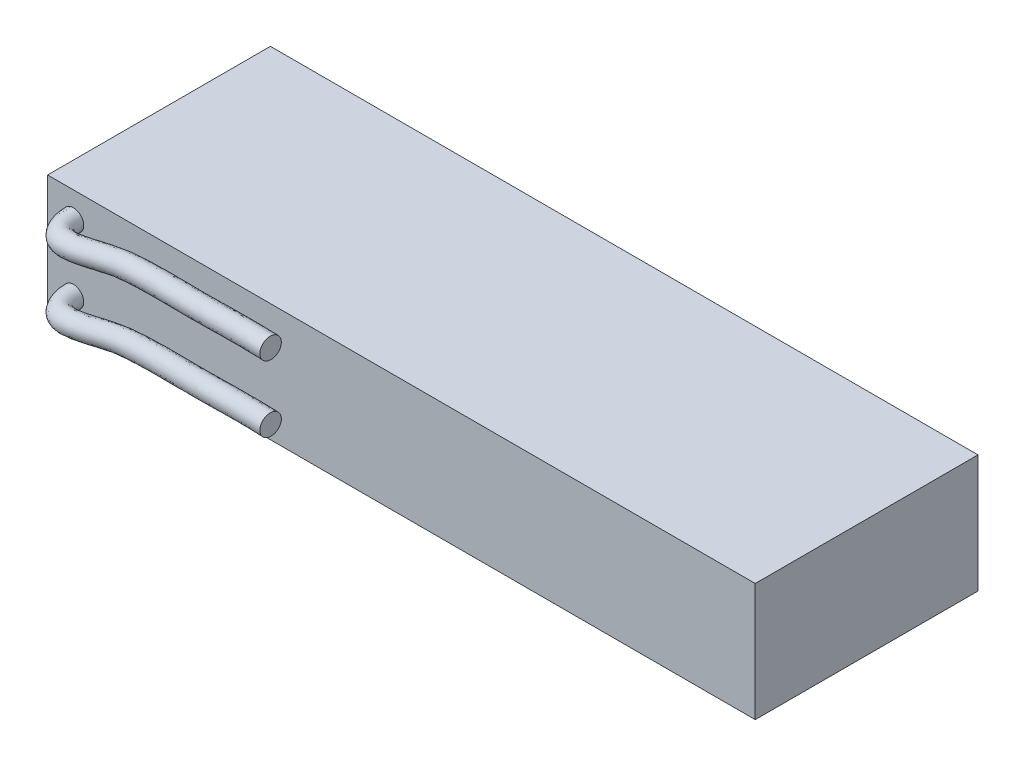
SolidWorks part; units mm, degrees
ref_plane "Front Plane" through (0, 0, 0) normal (0, 0, 1) x (1, 0, 0)
ref_plane "Top Plane" through (0, 0, 0) normal (0, 1, 0) x (1, 0, 0)
ref_plane "Right Plane" through (0, 0, 0) normal (1, 0, 0) x (0, 0, -1)
sketch "Sketch1" plane through (0, 0, 0) normal (0, 1, 0) x (1, 0, 0)
  line L1 (0, 0) -> (137.16, 0)
  line L2 (0, 0) -> (0, 43.18)
  line L3 (0, 43.18) -> (137.16, 43.18)
  line L4 (137.16, 0) -> (137.16, 43.18)
  dimension "D1" = 137.16
  dimension "D2" = 43.18
extrude "Boss-Extrude1" add sketch "Sketch1" along normal blind 22.86
sketch "Sketch2" plane through (0, 0, 0) normal (0, 0, 1) x (1, 0, 0)
  line L0 (0, 11.43) -> (137.16, 11.43) construction
  line L1 (0, 22.86) -> (0, 0) construction
  line L2 (137.16, 22.86) -> (137.16, 0) construction
  line L3 (0, 0) -> (137.16, 0) construction
  circle A1 centre (5, 5) radius 2
  circle A2 centre (5, 17.86) radius 2
  dimension "D1" = 4
  dimension "D2" = 5
  dimension "D3" = 5
ref_plane "Plane1" through (0, 5, 0) normal (0, -1, 0) x (-1, 0, 0)
sketch "Sketch3" plane through (0, 5, 0) normal (0, -1, 0) x (-1, 0, 0)
  line L0 (-7, 0) -> (-3, 0) construction
  line L1 (-5, 0) -> (-5, -6.8298) construction
  spline S0 degree 3 poles (-5, 0) (-5, -1.824) (-6.6605, -6.6948) (-14.525, -2.94) (-23.2093, -2.1686) (-28.1778, -2.467) (-38.3561, -2.3165) (-41.8094, -2.2588) (-45.6448, -2.4259) knots 0 0 0 0 0.144477 0.319453 0.373463 0.650005 0.716116 1 1 1 1
sweep "Sweep1" add profiles "Sketch2" path "Sketch3"
